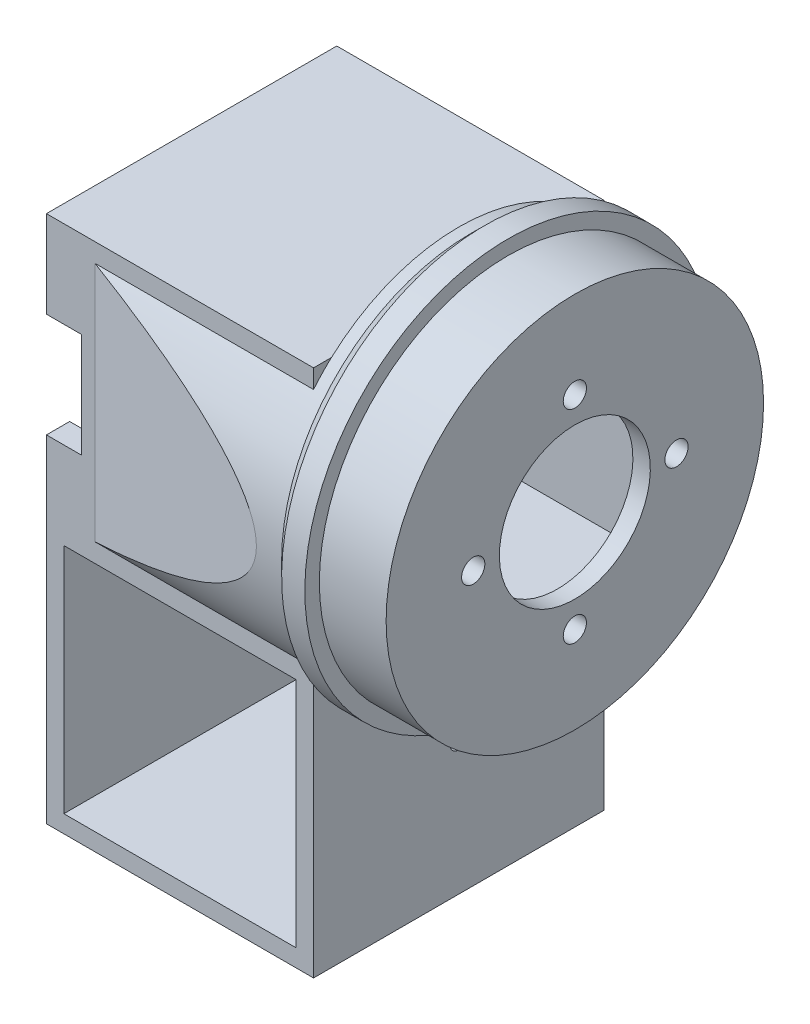
SolidWorks part; units mm, degrees
material "PA Type 6"
ref_plane "Front Plane" through (0, 0, 0) normal (0, 0, 1) x (1, 0, 0)
ref_plane "Top Plane" through (0, 0, 0) normal (0, 1, 0) x (1, 0, 0)
ref_plane "Right Plane" through (0, 0, 0) normal (1, 0, 0) x (0, 0, -1)
sketch "Esquisse1" plane through (0, 0, 0) normal (0, 0, 1) x (1, 0, 0)
  line L1 (-46, 46) -> (0, 46)
  line L2 (-46, 46) -> (-46, 0)
  line L3 (-46, 0) -> (0, 0)
  line L4 (0, 46) -> (0, 0)
  line L5 (-43, 43) -> (-3, 43)
  line L6 (-43, 43) -> (-43, 3)
  line L7 (-43, 3) -> (-3, 3)
  line L8 (-3, 43) -> (-3, 3)
  dimension "D1" = 46
  dimension "D2" = 40
  dimension "D3" = 3
  dimension "D4" = 3
extrude "Boss.-Extru.1" add sketch "Esquisse1" along normal blind 50
sketch "Esquisse2" plane through (0, 0, 0) normal (1, 0, 0) x (0, 0, -1)
  line L0 (-50, 0) -> (-50, 46) construction
  line L1 (-46, 88) -> (-4, 88)
  line L2 (-46, 88) -> (-46, 46)
  line L3 (-46, 46) -> (-4, 46)
  line L4 (-4, 88) -> (-4, 46)
  line L5 (-50, 43) -> (0, 43)
  line L6 (-50, 43) -> (-50, 91)
  line L7 (-50, 91) -> (0, 91)
  line L8 (0, 43) -> (0, 91)
  line L9 (-50, 46) -> (0, 46) construction
  line L10 (-25, 91) -> (-25, 43) construction
  dimension "D1" = 42
  dimension "D2" = 3
  dimension "D3" = 21
extrude "Boss.-Extru.2" add sketch "Esquisse2" against normal blind 46
sketch "Esquisse4" plane through (0, 0, 50) normal (0, 0, 1) x (1, 0, 0)
  line L0 (-46, 67) -> (-40, 67) construction
  line L1 (-46, 76) -> (-40, 76)
  line L2 (-46, 76) -> (-46, 58)
  line L3 (-46, 58) -> (-40, 58)
  line L4 (-40, 76) -> (-40, 58)
  line L6 (-46, 88) -> (-46, 46) construction
  point P6 (0, 0)
  dimension "D1" = 6
  dimension "D2" = 18
extrude "Enlèv. mat.-Extru.1" cut sketch "Esquisse4" against normal blind 6
sketch "Esquisse5" plane through (0, 0, 0) normal (1, 0, 0) x (0, 0, -1)
  line L0 (-46, 46) -> (-4, 88) construction
  line L2 (-46, 88) -> (-4, 88)
  line L3 (-46, 88) -> (-46, 46)
  line L4 (-46, 46) -> (-4, 46)
  line L5 (-4, 88) -> (-4, 46)
  circle A0 centre (-25, 67) radius 32.5
  dimension "D1" = 65
extrude "Boss.-Extru.3" add sketch "Esquisse5" along normal blind 17
sketch "Esquisse6" plane through (17, 0, 0) normal (1, 0, 0) x (0, 0, -1)
  circle A0 centre (-25, 67) radius 32.5
  circle A1 centre (-25, 67) radius 32.5 construction
  circle A2 centre (-25, 67) radius 17.5 construction
  circle A3 centre (-25, 84.5) radius 2
  circle A4 centre (-7.5, 67) radius 2
  circle A5 centre (-25, 49.5) radius 2
  circle A6 centre (-42.5, 67) radius 2
  circle A7 centre (-25, 67) radius 13
  dimension "D1" = 35
  dimension "D6" = 4
  dimension "D7" = 26
  dimension "D2" = 0
  dimension "D3" = 0
  dimension "D4" = 0
  dimension "D5" = 0
extrude "Boss.-Extru.4" add sketch "Esquisse6" along normal blind 3
chamfer "Chanfrein1" distance 8 angle 78 2 edges at (0, 67, 50) (0, 67, 0) first distance on face at (0, 67, 53.75) first distance on face at (0, 67, -3.75)
sketch "Esquisse7" plane through (0, 0, 0) normal (-1, 0, 0) x (0, 0, 1)
  circle A0 centre (25, 67) radius 35
  circle A1 centre (25, 67) radius 32.5
  arc A2 (0, 87.7666) -> (0, 46.2334) centre (25, 67) ccw construction
  dimension "D1" = 70
extrude "Boss.-Extru.5" add sketch "Esquisse7" against normal blind 3.5 from offset 5 offset against normal yes
chamfer "Chanfrein2" distance 3 angle 45 1 edges at (5, 34.5, 25)
sketch "Esquisse8" plane through (-46, 0, 0) normal (-1, 0, 0) x (0, 0, 1)
  line L0 (0, 3) -> (50, 43) construction
  circle A0 centre (25, 23) radius 1.5
  point P4 (0, 0)
  point P5 (0, 0)
  dimension "D1" = 3
extrude "Enlèv. mat.-Extru.2" cut sketch "Esquisse8" against normal through all
sketch "Esquisse9" plane through (0, 0, 0) normal (0, -1, 0) x (1, 0, 0)
  line L0 (-43, 0) -> (-3, 50) construction
  circle A0 centre (-23, 25) radius 1.5
  point P4 (0, 0)
  point P5 (0, 0)
  dimension "D1" = 3
extrude "Enlèv. mat.-Extru.3" cut sketch "Esquisse9" against normal blind 13.5
